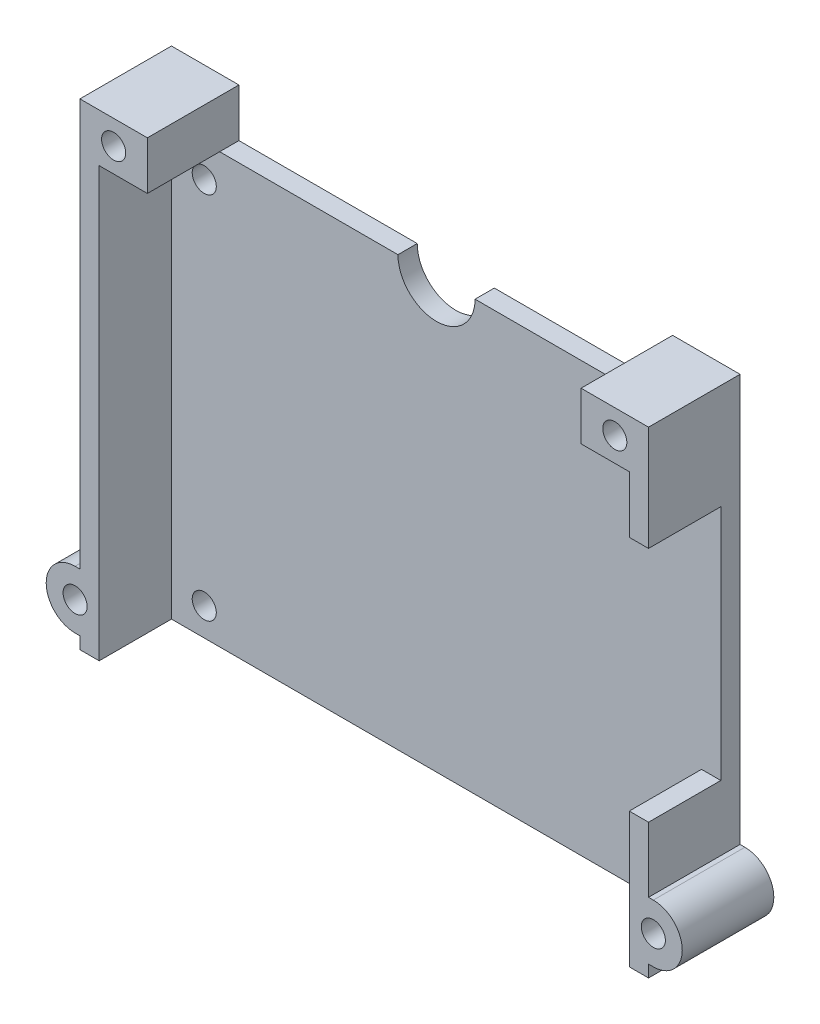
SolidWorks part; units mm, degrees
ref_plane "Front Plane" through (0, 0, 0) normal (0, 0, 1) x (1, 0, 0)
ref_plane "Top Plane" through (0, 0, 0) normal (0, 1, 0) x (1, 0, 0)
ref_plane "Right Plane" through (0, 0, 0) normal (1, 0, 0) x (0, 0, -1)
sketch "Sketch1" plane through (0, 0, 0) normal (0, 1, 0) x (1, 0, 0)
  line L0 (0, 0) -> (2, 0)
  line L1 (0, 0) -> (59, 0) construction
  line L2 (0, 0) -> (0, 9.5)
  line L3 (0, 9.5) -> (59, 9.5)
  line L4 (59, 0) -> (59, 9.5)
  line L5 (2, 0) -> (2, 7.5)
  line L6 (2, 7.5) -> (57, 7.5)
  line L7 (57, 7.5) -> (57, 0)
  line L8 (57, 0) -> (59, 0)
  dimension "D1" = 59
  dimension "D2" = 9.5
  dimension "D3" = 2
  dimension "D4" = 7.5
  dimension "D5" = 55
extrude "Boss-Extrude1" add sketch "Sketch1" along normal blind 44.5
sketch "Sketch2" plane through (59, 0, 0) normal (1, 0, 0) x (0, 0, -1)
  line L0 (0, 0) -> (0, 14) construction
  line L1 (0, 44.5) -> (0, 0) construction
  line L2 (0, 14) -> (7.5, 14)
  line L3 (7.5, 14) -> (7.5, 38.6)
  line L4 (7.5, 38.6) -> (0, 38.6)
  line L5 (0, 38.6) -> (0, 14)
  dimension "D1" = 14
  dimension "D2" = 7.5
  dimension "D3" = 24.6
extrude "Cut-Extrude1" cut sketch "Sketch2" against normal blind 10
sketch "Sketch3" plane through (0, 0, -9.5) normal (0, 0, -1) x (-1, 0, 0)
  line L0 (-59, 0) -> (-59, 7.25) construction
  line L1 (-59, 44.5) -> (-59, 0) construction
  line L2 (-59, 7.25) -> (-59, 1.25)
  line L3 (-59, 4.25) -> (-59.5, 4.25) construction
  line L4 (-59, 7.25) -> (-59.5, 7.25)
  line L5 (-59, 1.25) -> (-59.5, 1.25)
  line L6 (0, 0) -> (0, 7.25) construction
  line L7 (0, 44.5) -> (0, 0) construction
  line L8 (0, 7.25) -> (0.5, 7.25)
  line L9 (0, 7.25) -> (0, 1.25)
  line L10 (0, 1.25) -> (0.5, 1.25)
  line L11 (0, 4.25) -> (0.5, 4.25) construction
  arc A0 (-59.5, 7.25) -> (-59.5, 1.25) centre (-59.5, 4.25) ccw
  circle A1 centre (-59.5, 4.25) radius 1.25
  arc A2 (0.5, 7.25) -> (0.5, 1.25) centre (0.5, 4.25) cw
  circle A3 centre (0.5, 4.25) radius 1.25
  line M5 (0, 0) -> (0, 44.5)
  line M7 (-59, 44.5) -> (-59, 0)
  dimension "D4" = 3
  dimension "D5" = 2.5
  dimension "D11" = 3
  dimension "D12" = 2.5
  dimension "D1" = 7.25
  dimension "D2" = 6
  dimension "D3" = 0.5
  dimension "D6" = 7.25
  dimension "D7" = 0.5
  dimension "D8" = 6
  dimension "D9" = 0.5
extrude "Boss-Extrude2" add sketch "Sketch3" against normal blind 9.5 contours A1 L4 A0 L5 M7 | A3 L10 A2 L8 M5 region at (59.0695, 6.3228, -9.5) region at (-0.25, 7.1805, -9.5)
extrude "Cut-Extrude2" cut sketch "Sketch3<3>" against normal blind 11 contours L2 A1 | L9 A3 region at (58.6906, 4.25, -9.5) region at (0.3094, 4.25, -9.5)
sketch "Sketch3<3>" plane through (0, 0, -9.5) normal (0, 0, -1) x (-1, 0, 0) same geometry as "Sketch3"
sketch "Sketch4" plane through (0, 44.5, 0) normal (0, 1, 0) x (1, 0, 0)
  line L0 (59, 9.5) -> (0, 9.5) construction
  line L1 (0, 0) -> (7, 0)
  line L2 (0, 0) -> (0, 9.5)
  line L3 (0, 9.5) -> (7, 9.5)
  line L4 (7, 0) -> (7, 9.5)
  line L6 (59, 0) -> (52, 0)
  line L7 (59, 0) -> (59, 9.5)
  line L8 (59, 9.5) -> (52, 9.5)
  line L9 (52, 0) -> (52, 9.5)
  dimension "D1" = 7
  dimension "D2" = 7
extrude "Boss-Extrude3" add sketch "Sketch4" along normal blind 5
sketch "Sketch5" plane through (0, 0, -9.5) normal (0, 0, -1) x (-1, 0, 0)
  line L0 (-59, 49.5) -> (-52, 44.5) construction
  line L1 (0, 49.5) -> (-7, 44.5) construction
  circle A0 centre (-55.5, 47) radius 1.25
  circle A1 centre (-3.5, 47) radius 1.25
  dimension "D1" = 2.5
  dimension "D2" = 2.5
extrude "Cut-Extrude3" cut sketch "Sketch5" against normal through all
sketch "Sketch7" plane through (0, 0, -9.5) normal (0, 0, -1) x (-1, 0, 0)
  line L0 (-59, 0) -> (-59, 2.9) construction
  line L1 (-59, 1.25) -> (-59, 0) construction
  line L2 (-59, 2.9) -> (0, 2.9) construction
  line L3 (0, 1.25) -> (0, 0) construction
  line L4 (-53.6, 2.9) -> (-5.4, 2.9)
  line L5 (-53.6, 2.9) -> (-53.6, 41.2) construction
  line L6 (-53.6, 41.2) -> (-5.4, 41.2) construction
  circle A0 centre (-53.6, 2.9) radius 1.25
  circle A1 centre (-5.4, 2.9) radius 1.25
  circle A2 centre (-53.6, 41.2) radius 1.25
  circle A3 centre (-5.4, 41.2) radius 1.25
  point P11 (-29.5, 2.9)
  dimension "D3" = 2.5
  dimension "D4" = 2.5
  dimension "D6" = 2.5
  dimension "D8" = 2.5
  dimension "D1" = 2.9
  dimension "D2" = 48.2
  dimension "D5" = 38.3
  dimension "D7" = 48.2
extrude "Cut-Extrude4" cut sketch "Sketch7" against normal blind 10 contours A2 | A3 | A1 | A0 region at (5.4, 4.1146, -9.5) region at (54.8146, 2.9, -9.5) region at (53.6, 41.2, -9.5) region at (5.4, 41.2, -9.5)
sketch "Sketch8" plane through (0, 0, -9.5) normal (0, 0, -1) x (-1, 0, 0)
  line L0 (-52, 44.5) -> (-7, 44.5) construction
  circle A0 centre (-29.5, 44.5) radius 4
  dimension "D1" = 8
extrude "Cut-Extrude5" cut sketch "Sketch8" against normal through all
